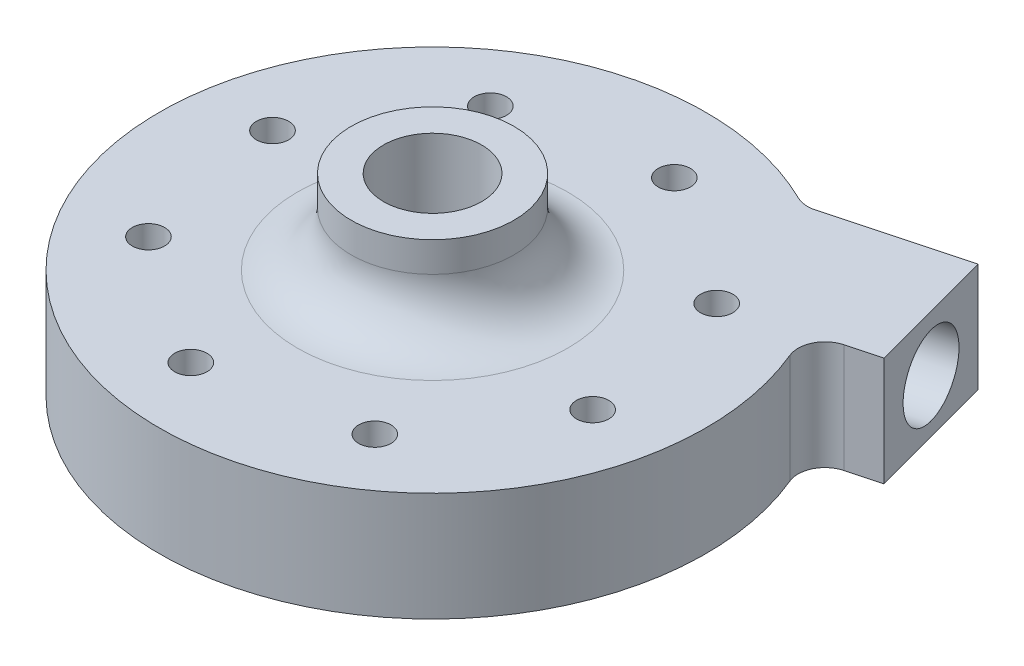
SolidWorks part; units mm, degrees
material "1060 Alloy"
ref_plane "Front" through (0, 0, 0) normal (0, 0, 1) x (1, 0, 0)
ref_plane "Top" through (0, 0, 0) normal (0, 1, 0) x (1, 0, 0)
ref_plane "Right" through (0, 0, 0) normal (1, 0, 0) x (0, 0, -1)
sketch "Sketch1" plane through (0, 0, 0) normal (0, 1, 0) x (1, 0, 0)
  circle A4 centre (0, 0) radius 101.6
  point P0 (0, 0)
  point P17 (0, 0)
  dimension "D1" = 203.2
extrude "body extrusion" add sketch "Sketch1" along normal blind 50.8
sketch "Sketch7" plane through (0, 50.8, 0) normal (0, 1, 0) x (1, 0, 0)
  circle A0 centre (0, 0) radius 9.1281
  dimension "D1" = 18.2562
extrude "inlet tap" cut sketch "Sketch7" against normal blind 20
sketch "Sketch6" plane through (0, 50.8, 0) normal (0, 1, 0) x (1, 0, 0)
  circle A0 centre (0, 0) radius 5.4102
  dimension "D1" = 10.8204
extrude "De" cut sketch "Sketch6" against normal blind 100
sketch "Sketch2" plane through (0, 0, 0) normal (0, 0, 1) x (1, 0, 0)
  line L0 (0, 19.9705) -> (0, 26.8)
  line L1 (0, 26.8) -> (5.4102, 26.8)
  line L2 (5.4102, 26.8) -> (27.1319, 26.7805)
  line L3 (27.1319, 26.7805) -> (27.1319, 19.9705)
  line L4 (27.1319, 19.9705) -> (0, 19.9705) construction
  line L6 (9.1281, 30.8) -> (-9.1281, 30.8) construction
  line L7 (0, 19.9705) -> (0, 0)
  line L8 (0, 0) -> (27.1319, 0)
  line L9 (-101.6, 0) -> (101.6, 0) construction
  line L10 (27.1319, 0) -> (27.1319, 19.9705)
  dimension "D1" = 27.1319
  dimension "D3" = 6.81
  dimension "D2" = 5.4102
  dimension "D4" = 6.8295
  dimension "D5" = 4
revolve "main chamber" cut sketch "Sketch2" angle 360 about L0
sketch "outlet axis plane ref 1" plane through (0, 0, 0) normal (0, -1, 0) x (1, 0, 0)
  line L0 (0, 0) -> (0, -27.1319) construction
  line L1 (0, -27.1319) -> (83.6978, -57.5954) construction
  line L2 (4.5256, -26.7518) -> (88.8165, -49.3375) construction
  line L3 (4.5256, -26.7518) -> (0, -25.5392) construction
  circle A0 centre (0, 0) radius 27.1319 construction
  circle A1 centre (0, 0) radius 101.6 construction
  dimension "D1" = 110
  dimension "D2" = 1.905
  dimension "D3" = 5
sketch "outlet axis plane ref 2" plane through (0, 50.8, 0) normal (0, 1, 0) x (1, 0, 0)
  line L0 (0, 25.5392) -> (88.8165, 49.3375) construction
ref_plane "outlet axial plane" through (-6.3848, 0, -23.8284) normal (0.2588, 0, 0.9659) x (0.9659, 0, -0.2588)
sketch "Sketch11" plane through (-6.3848, 0, -23.8284) normal (0.2588, 0, 0.9659) x (0.9659, 0, -0.2588)
  line L0 (6.61, 50.8) -> (6.61, 0) construction
  line L1 (6.61, 24.8755) -> (106.61, 24.8755) construction
  line L2 (6.61, 26.3706) -> (106.2295, 35.0861)
  line L4 (6.61, 26.3706) -> (6.61, 24.8755)
  line L5 (6.61, 24.8755) -> (106.2295, 24.8755)
  line L6 (106.2295, 24.8755) -> (106.2295, 35.0861)
  line L7 (11.2952, 0) -> (11.2952, 26.7805) construction
  line L8 (11.2952, 0) -> (6.61, 0) construction
  line L10 (7.0223, 0) -> (95.7527, 0) construction
  line L11 (27.1319, 26.7805) -> (-27.1319, 26.7805) construction
  dimension "D3" = 5
  dimension "D2" = 100
  dimension "D4" = 100
  dimension "D1" = 1.905
revolve "conical outlet" cut sketch "Sketch11" angle 360 about L5
sketch "exit normal plane ref 1" plane through (0, 50.8, 0) normal (0, 1, 0) x (1, 0, 0)
  line L0 (0.0212, 27.1319) -> (39.9716, 41.6726) construction
  line L1 (83.7021, 57.5893) -> (0.0212, 27.1319) construction
  line L2 (83.7021, 57.5893) -> (0.0212, 27.1319) construction
  line L3 (8.9658, 25.6077) -> (93.1964, 40.4598) construction
  line L4 (8.9658, 25.6077) -> (93.1964, 40.4598) construction
  line L5 (8.9658, 25.6077) -> (93.1964, 40.4598) construction
  line L6 (4.5256, 26.7518) -> (88.8165, 49.3375)
  line L7 (41.3273, 36.6128) -> (42.6831, 31.553)
  line L8 (41.3273, 36.6128) -> (39.9716, 41.6726)
  line L9 (8.9658, 25.6077) -> (93.1964, 40.4598) construction
  arc A0 (4.5256, 26.7518) -> (6.0711, 26.4439) centre (0, 0) ccw construction
  circle A3 centre (0, 0) radius 101.6 construction
  dimension "D1" = 5
  dimension "D2" = 5
  dimension "D3" = 38.1
sketch "exit normal plane ref 2" plane through (0, 0, 0) normal (0, -1, 0) x (1, 0, 0)
  line L0 (42.6831, -31.553) -> (39.9716, -41.6726)
ref_plane "outlet normal plane" through (47.7121, 0, -12.7844) normal (0.9659, 0, -0.2588) x (-0.2588, 0, -0.9659)
sketch "Sketch18" plane through (0, 50.8, 0) normal (0, 1, 0) x (1, 0, 0)
  line L0 (49.724, 51.6403) -> (25.8941, 45.2551)
  line L1 (41.3273, 36.6128) -> (39.9716, 41.6726) construction
  line L2 (52.9184, 39.7186) -> (49.724, 51.6403) construction
  line L4 (50.2416, 26.2238) -> (56.1128, 27.797)
  line L5 (49.724, 51.6403) -> (56.1128, 27.797)
  line L6 (-24.9807, 18.8456) -> (12.2111, 28.8111) construction
  arc A0 (22.3957, 45.5968) -> (46.9178, 19.4771) centre (0, 0) ccw
  arc A2 (25.8941, 45.2551) -> (22.3957, 45.5968) centre (24.6, 50.0847) cw
  circle A3 centre (0, 0) radius 101.6 construction
  circle A4 centre (0, 0) radius 152.4
  arc A5 (50.2416, 26.2238) -> (46.9178, 19.4771) centre (51.5357, 21.3942) ccw
  dimension "D1" = 101.6
  dimension "D4" = 5
  dimension "D2" = 12.3422
  dimension "D3" = 12.3422
  dimension "D5" = 50.8
  dimension "D6" = 12
extrude "top profile" cut sketch "Sketch18" against normal blind 76.2
sketch "Sketch19" plane through (59.3032, 0, -15.8903) normal (0.9659, 0, -0.2588) x (-0.2588, 0, -0.9659)
  line L0 (24.669, 50.8) -> (24.669, 24.8755) construction
  line L4 (24.669, 50.8) -> (29.9073, 50.8) construction
  line L7 (24.669, 50.8) -> (19.4306, 50.8) construction
  line L10 (12.3268, 50.8) -> (37.0112, 50.8) construction
  circle A1 centre (24.669, 24.8755) radius 7.3422
  dimension "D1" = 14.6844
extrude "outlet tap" cut sketch "Sketch19" against normal blind 12
sketch "Sketch14" plane through (0, 0, 0) normal (0, 0, 1) x (1, 0, 0)
  line L0 (15.1281, 50.8) -> (15.1281, 35.2177)
  line L3 (15.1281, 35.2177) -> (50.8, 35.2177)
  line L5 (0, 0) -> (0, 14.9705)
  line L6 (-27.1319, 0) -> (27.1319, 0) construction
  line L7 (0, 14.9705) -> (50.8, 14.9705)
  line L8 (50.8, 14.9705) -> (50.8, 0) construction
  line L9 (50.8, 0) -> (0, 0)
  line L10 (52.9184, 32.2177) -> (41.3273, 32.2177) construction
  line L12 (27.1319, 26.7805) -> (-27.1319, 26.7805) construction
  line L13 (0, 50.8) -> (88.8165, 50.8) construction
  line L14 (15.1281, 50.8) -> (50.8, 50.8)
  line L15 (50.8, 50.8) -> (50.8, 35.2177) construction
  line L16 (9.1281, 30.8) -> (9.1281, 50.8) construction
  line L17 (50.8, 0) -> (50.8, 50.8) construction
  line L19 (50.8, 50.8) -> (127, 50.8)
  line L21 (50.8, 50.8) -> (50.8, 35.2177) construction
  line L22 (50.8, 35.2177) -> (127, 35.2177)
  line L23 (127, 50.8) -> (127, 35.2177)
  line L24 (50.8, 14.9705) -> (127, 14.9705)
  line L25 (50.8, 14.9705) -> (50.8, 0) construction
  line L26 (50.8, 0) -> (127, 0)
  line L27 (127, 14.9705) -> (127, 0)
  dimension "D3" = 6
  dimension "D1" = 11.81
  dimension "D2" = 3
  dimension "D5" = 76.2
revolve "upper lower cuts" cut sketch "Sketch14" angle 360 about L5
sketch "Sketch20" plane through (0, 35.2177, 0) normal (0, 1, 0) x (1, 0, 0)
  line L0 (39.9716, 41.6726) -> (0.0212, 27.1319) construction
  circle A0 centre (0, 0) radius 38.1 construction
  circle A1 centre (7.5907, 37.3362) radius 3
  dimension "D1" = 76.2
  dimension "D2" = 6
extrude "bolts" cut sketch "Sketch20" against normal blind 76.2
pattern_circular "bolt pattern" count 8 over 360 about axis through (0, 35.2177, 0) along (0, 1, 0) of "bolts"
fillet "Fillet1" radius 10 1 edges at (0, 35.2177, -15.1281)
equation "\"de\" = 0.426in"
equation "\"D1@body extrusion\"=2in"
equation "\"D2@Sketch2\"=\"de\"/2"
equation "\"D3@Sketch2\"=\"impeller cavity outer height\""
equation "\"D1@Sketch2\"=\"impeller cavity diameter\"/2"
equation "\"D1@Sketch6\"=\"de\""
equation "\"D1@De\" = 100mm"
equation "\"D1@Sketch7\"=\"impeller housing threaded inlet diameter\""
equation "\"D1@inlet tap\" = \"impeller housing threaded inlet depth\""
equation "\"D4@Sketch2\"=\"impeller cavity center height\""
equation "\"z\" = 12"
equation "\"d2\" = 2.097in"
equation "\"d_exit\" =\"b2\""
equation "\"theta\" = 15"
equation "\"b2\" = .15in"
equation "\"b1\" = \"b2\" + (\"d2\"/2 - \"de\"/2)*sin(\"theta\")"
equation "\"s\" = ( 1/\"z\")*(3.14*\"de\" - (3.14*(\"de\"^2) / (4*(\"b1\"))))"
equation "\"s_opening\" = (3.14*\"de\" - \"z\"*\"s\")/\"z\""
equation "\"area_eye\"=3.14*(\"de\"^2)/4"
equation "\"single_channel_area\"=\"s_opening\"*\"b1\""
equation "\"impeller upper clearance\"= .5mm"
equation "\"impeller horizontal clearance\"= .5mm"
equation "\"impeller bottom clearance\"= .5mm"
equation "\"impeller base thickness\"= 2mm"
equation "\"impeller boss depth\" = \"shaft impeller section length\" + 3mm + \"impeller bolt head depth\" - \"impeller base thickness\""
equation "\"impeller cavity center height\"= \"impeller bottom clearance\" + \"impeller upper clearance\" + \"final impeller center height\""
equation "\"impeller cavity diameter\"= 2 * \"impeller horizontal clearance\" + \"d2\""
equation "\"impeller cavity outer height\"= \"impeller bottom clearance\" + \"impeller upper clearance\" + \"impeller base thickness\" + \"b2\""
equation "\"impeller housing bolt count\" = 8"
equation "\"impeller housing bolt diameter\" = 6mm"
equation "\"impeller housing bolt pattern diameter\" = 3in"
equation "\"impeller housing o-ring channel height\"= 1.5mm"
equation "\"impeller housing o ring channel width\"= 1.5mm"
equation "\"impeller housing o-ring diameter\" = 2in"
equation "\"impeller housing threaded inlet diameter\" = 0.71875in 'this is the 23/32 drill size for 1/2 in npt fitting"
equation "\"impeller housing threaded inlet depth\"= 20mm"
equation "\"impeller housing thickness\"= \"impeller housing threaded inlet depth\" + \"impeller cavity center height\"+ 4mm"
equation "\"impeller housing exit threaded diameter\"= 0.578125in 'this is the 37/64 drill size for 3/8 npt fitting"
equation "\"impeller housing exit threaded depth\"= 12mm"
equation "\"impeller housing diameter\" = 4in"
equation "\"impeller housing diffuser conical angle\"=10"
equation "\"impeller housing diffuser tangent angle\"=20"
equation "\"motor to housing distance\" = \"motor shaft pride\" + \"shaft coupler section length\" - \"bearing plate bearing stop depth\" + 2mm"
equation "\"D1@outlet axis plane ref 1\" = \"impeller housing diffuser tangent angle\" + 90"
equation "\"D2@outlet axis plane ref 1\" = \"d_exit\" / 2"
equation "\"D3@outlet axis plane ref 1\" = \"impeller housing diffuser conical angle\" / 2"
equation "\"D1@Sketch11\"=\"d_exit\"/2"
equation "\"D3@Sketch11\"=\"impeller housing diffuser conical angle\"/2"
equation "\"D1@exit normal plane ref 1\"=\"impeller housing diffuser conical angle\" / 2"
equation "\"impeller housing outlet purchase\" = 5mm"
equation "\"D1@Sketch14\"=\"impeller housing outlet purchase\"+ \"impeller cavity outer height\""
equation "\"bearing OD\" = 30mm"
equation "\"bearing outer race thickness\"= 1mm"
equation "\"bearing ID\"= 10mm"
equation "\"bearing depth\"= 9mm"
equation "\"bearing inner race thickness\"= 1mm"
equation "\"small seal OD\" = 20mm"
equation "\"small seal ID\"= 8mm"
equation "\"small seal depth\" = 8.3mm"
equation "\"big seal OD\" = 27mm"
equation "\"big seal ID\"= 15mm"
equation "\"big seal depth\"= 8.3mm"
equation "\"bit size\" = 2mm"
equation "\"inlet area before cut\" = \"bit size\" * (\"z\") * \"b1\""
equation "\"area to cut\" = \"inlet area before cut\" - \"area_eye\""
equation "\"height to cut\" = \"area to cut\" / ((\"z\")* \"bit size\")"
equation "\"final impeller center height\" = \"impeller base thickness\" + \"b1\" - \"height to cut\""
equation "\"bearing bore\" = \"bearing depth\" + 1mm"
equation "\"small seal bore\" = \"small seal depth\" + 1mm"
equation "\"big seal bore\" = \"big seal depth\" + 1mm"
equation "\"impeller boss diameter\" = \"big seal ID\""
equation "\"impeller dowel diameter\" = 2mm"
equation "\"impeller bolt head diameter\" = 7.5mm"
equation "\"impeller bolt head depth\" = 4mm"
equation "\"impeller shaft bore\"= 8mm"
equation "\"impeller shaft bore depth\" = \"impeller boss depth\" + \"impeller base thickness\" - \"impeller bolt head depth\" - 3mm"
equation "\"impeller dowel length\" = 2mm*2 + \"impeller shaft bore\""
equation "\"impeller screw hole bore\" = 4mm"
equation "\"shaft impeller screw hole diameter\" = \"impeller screw hole bore\""
equation "\"shaft impeller section length\" = \"big seal plate thickness\" + \"impeller bottom clearance\" + \"impeller base thickness\" - \"impeller bolt head depth\" - 3mm"
equation "\"shaft impeller screw hole depth\" = \"shaft impeller section length\"-\"impeller dowel diameter\"-2mm"
equation "\"shaft impeller section diameter\" = \"impeller shaft bore\""
equation "\"shaft seal section diameter\"=\"small seal ID\""
equation "\"shaft seal section length\"=\"small seal bore\" + 2mm"
equation "\"shaft bearing section diameter\" = \"bearing ID\""
equation "\"shaft bearing section length\" = \"bearing bore\""
equation "\"shaft bearing stop diameter\" = \"bearing ID\" + 2mm"
equation "\"shaft bearing stop length\" = 2mm"
equation "\"shaft coupler section diameter\" = 8mm"
equation "\"shaft coupler section length\" = \"shaft bearing stop length\" + \"coupler length\"/2 + 4mm"
equation "\"coupler motor shaft hole ID\"= 8mm"
equation "\"coupler OD\"= 17mm"
equation "\"coupler length\"= 25mm"
equation "\"square plate diameter\" = 3in"
equation "\"square plate bolt pattern diameter\"= 2in"
equation "\"square plate bolt hole ID\" = 8mm"
equation "\"bearing plate bearing stop ID\" = \"bearing OD\" - 4mm"
equation "\"bearing plate bearing stop depth\" = 3mm"
equation "\"bearing plate thickness\" = \"bearing bore\" + \"bearing plate bearing stop depth\""
equation "\"small seal plate lip depth\" = \"shaft bearing stop length\" + 1mm"
equation "\"small seal plate lip ID\" = \"small seal OD\" - 3mm"
equation "\"small seal plate thickness\" = \"small seal plate lip depth\" + \"small seal bore\""
equation "\"big seal plate lip depth\" = 8mm"
equation "\"big seal plate thickness\" = \"big seal plate lip depth\" + \"big seal bore\""
equation "\"big seal plate pressure hole diameter\" = .078125 'this is 5/64 drill "
equation "\"big seal plate pressure tap diameter\" = .34375in 'this is 11/32 drill for a 1/8 ANPT tap"
equation "\"big seal plate pressure tap depth\" = 9mm"
equation "\"motor mount coupler hole diameter\"= \"coupler OD\"+ 4mm"
equation "\"motor mount to housing post radius\"= ( 3 * \"square plate bolt hole ID\" ) / 2"
equation "\"motor mount m4 screw hole diameter\"= 4mm"
equation "\"motor mount m4 head diameter\"= 7.25mm"
equation "\"motor mount m4 head depth\"= 4mm"
equation "\"motor mount m4 pattern diamater\" = 30mm"
equation "\"motor mount plate thickness\"= 8mm + \"motor mount m4 head depth\""
equation "\"motor shaft pride\"= 32mm"
equation "\"motor shaft flat section length from tip\"= 25.7mm"
equation "\"motor shaft bore end clearance\"= 2mm"
equation "\"coupler shaft to motor clearance\" = 2mm"
equation "\"motor mount shaft hole depth\"= \"motor shaft pride\""
equation "\"D1@Sketch18\"=\"impeller housing diameter\""
equation "\"D2@Sketch18\"=\"impeller housing exit threaded diameter\"/2+5mm"
equation "\"D3@Sketch18\"=\"impeller housing exit threaded diameter\"/2+5mm"
equation "\"D1@Sketch19\"=\"impeller housing exit threaded diameter\""
equation "\"D1@outlet tap\" = \"impeller housing exit threaded depth\""
equation "\"D1@Sketch20\"=\"impeller housing bolt pattern diameter\" "
equation "\"D2@Sketch20\"=\"impeller housing bolt diameter\""
equation "\"D3@Sketch20\"=\"impeller housing bolt diameter\"+1mm"
equation "\"D1@bolt pattern\" = \"impeller housing bolt count\""
equation "\"D2@exit normal plane ref 1\"=\"impeller housing diffuser conical angle\" / 2"
equation "\"impeller housing diffuser length\" = 1.5in"
equation "\"D3@exit normal plane ref 1\"=\"impeller housing diffuser length\""
equation "\"D6@Sketch18\"=\"impeller housing exit threaded depth\""
